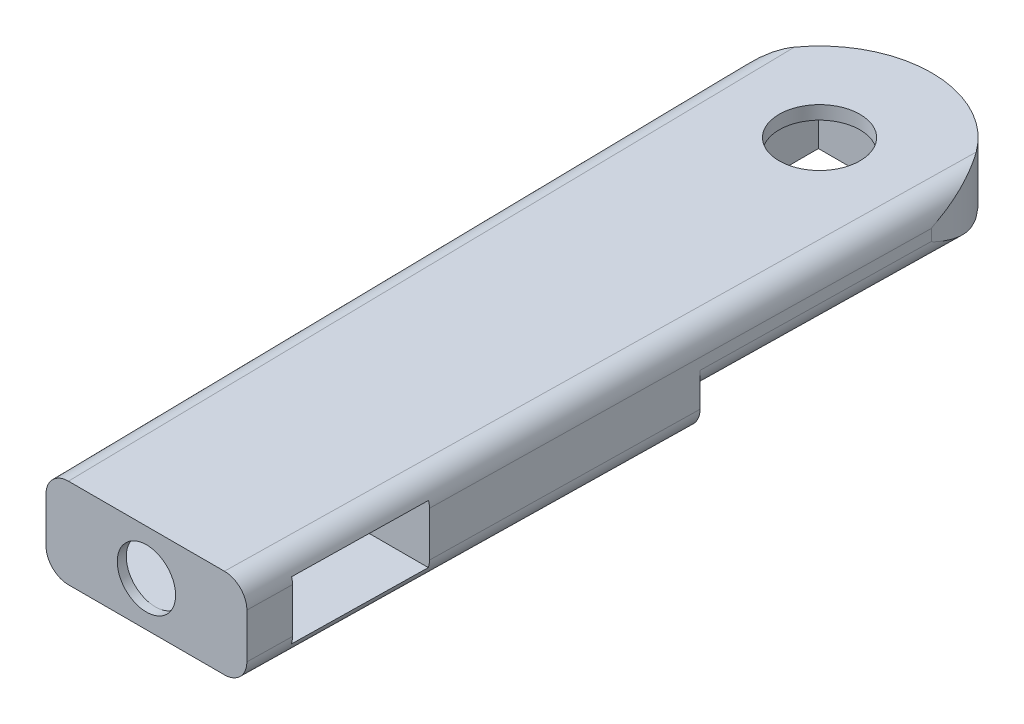
SolidWorks part; units mm, degrees
material "ABS"
ref_plane "Front Plane" through (0, 0, 0) normal (0, 0, 1) x (1, 0, 0)
ref_plane "Top Plane" through (0, 0, 0) normal (0, 1, 0) x (1, 0, 0)
ref_plane "Right Plane" through (0, 0, 0) normal (1, 0, 0) x (0, 0, -1)
sketch "Sketch1" plane through (0, 0, 0) normal (0, 1, 0) x (1, 0, 0)
  line L0 (0, 125.7123) -> (0, -325.7123) construction
  line L1 (-170.4269, -100) -> (232.1141, -100) construction
  line L2 (-25, 0) -> (41.6105, 0) construction
  line L3 (-25, 0) -> (-22.3817, -150)
  line L4 (25, 0) -> (22.3817, -150)
  line L5 (22.3817, -150) -> (-22.3817, -150)
  arc A2 (25, 0) -> (-25, 0) centre (0, 0) ccw
  point P7 (0, -100)
  dimension "D1" = 89
  dimension "D2" = 89
  dimension "D3" = 150
extrude "Boss-Extrude1" add sketch "Sketch1" along normal blind 20
sketch "Sketch7" plane through (0, 0, 0) normal (1, 0, 0) x (0, 0, -1)
  line L0 (-150, 20) -> (-150, 0) construction
  line L1 (-110, 16.4217) -> (-140, 16.4217)
  line L2 (-110, 16.4217) -> (-110, 3.4217)
  line L3 (-110, 3.4217) -> (-140, 3.4217)
  line L4 (-140, 16.4217) -> (-140, 3.4217)
  dimension "D1" = 10
  dimension "D2" = 13
  dimension "D3" = 30
extrude "Cut-Extrude5" cut sketch "Sketch7" against normal through all both and the other way through all
sketch "Sketch8" plane through (0, 0, 140) normal (0, 0, -1) x (-1, 0, 0)
  line L0 (22.5563, 16.4217) -> (22.5563, 3.4217) construction
  line L1 (17.3963, 3.4217) -> (-7.2037, 3.4217)
  line L2 (17.3963, 3.4217) -> (17.3963, 16.4217)
  line L3 (17.3963, 16.4217) -> (-7.2037, 16.4217)
  line L4 (-7.2037, 3.4217) -> (-7.2037, 16.4217)
  line L5 (22.5563, 16.4217) -> (-22.5563, 16.4217) construction
  line L6 (22.5563, 3.4217) -> (-22.5563, 3.4217) construction
  dimension "D1" = 24.6
  dimension "D2" = 5.16
  dimension "D3" = 0
  dimension "D4" = 0
extrude "Cut-Extrude6" cut sketch "Sketch8" against normal blind 8
sketch "Sketch9" plane through (0, 0, 148) normal (0, 0, -1) x (-1, 0, 0)
  line L1 (-22.3817, 20) -> (-22.3817, 0) construction
  line L2 (17.3963, 16.4217) -> (-7.2037, 16.4217) construction
  circle A0 centre (-0.0017, 9.9217) radius 6.5
  dimension "D1" = 13
  dimension "D3" = 6.5
  dimension "D2" = 22.38
extrude "Cut-Extrude7" cut sketch "Sketch9" against normal blind 8
sketch "Sketch10" plane through (0, 0, 0) normal (0, -1, 0) x (1, 0, 0)
  line L1 (10.5, 30.75) -> (-10.5, 30.75)
  line L2 (10.5, 30.75) -> (10.5, -10.25)
  line L3 (10.5, -10.25) -> (-10.5, -10.25)
  line L4 (-10.5, 30.75) -> (-10.5, -10.25)
  arc A0 (-25, 0) -> (25, 0) centre (0, 0) ccw construction
  point P9 (0, -25)
  dimension "D1" = 41
  dimension "D2" = 21
  dimension "D3" = 14.5
  dimension "D4" = 14.75
extrude "Cut-Extrude8" cut sketch "Sketch10" against normal blind 17
sketch "Sketch12" plane through (0, 17, 0) normal (0, -1, 0) x (-1, 0, 0)
  circle A0 centre (0, 0) radius 9
  dimension "D1" = 18
extrude "Cut-Extrude9" cut sketch "Sketch12" against normal blind 12
sketch "Sketch14" plane through (0, 0, 0) normal (0, -1, 0) x (-1, 0, 0)
  line L0 (-10.5, -30.75) -> (10.5, -30.75) construction
  line L1 (10.5, -30.75) -> (10.5, 10.25) construction
  line L2 (-10.5, 10.25) -> (-10.5, -30.75) construction
  line L3 (10.5, 10.25) -> (-10.5, 10.25) construction
  circle A0 centre (-5, -35.45) radius 2
  circle A1 centre (5, -35.45) radius 2
  circle A2 centre (5, 14.95) radius 2
  circle A3 centre (-5, 14.95) radius 2
  dimension "D1" = 4
  dimension "D2" = 4
  dimension "D3" = 4
  dimension "D4" = 4
  dimension "D6" = 4.7
  dimension "D8" = 5.5
  dimension "D9" = 5.5
  dimension "D10" = 5.5
  dimension "D11" = 4.7
  dimension "D12" = 4.7
  dimension "D5" = 4.7
  dimension "D7" = 5.5
extrude "Cut-Extrude11" cut sketch "Sketch14" against normal blind 11.5
sketch "Sketch15" plane through (0, 0, 0) normal (0, -1, 0) x (1, 0, 0)
  line L0 (10.5, 30.75) -> (-10.5, 30.75) construction
  line L1 (37.5576, 50.75) -> (-41.9671, 50.75)
  line L2 (37.5576, 50.75) -> (37.5576, -38.9325)
  line L3 (37.5576, -38.9325) -> (-41.9671, -38.9325)
  line L4 (-41.9671, 50.75) -> (-41.9671, -38.9325)
  dimension "D1" = 20
extrude "Cut-Extrude12" cut sketch "Sketch15" against normal blind 7.5
fillet "Fillet1" radius 5 6 edges at (-23.6909, 20, 75) (-23.2479, 0, 100.375) (-24.5571, 7.5, 25.375) (24.5571, 7.5, 25.375) (23.6909, 20, 75) (23.2479, 0, 100.375)
sketch "Sketch16" plane through (0, 0, 140) normal (0, 0, -1) x (-1, 0, 0)
  circle A0 centre (-8.7017, 9.9217) radius 1
  circle A1 centre (18.8983, 9.9217) radius 1
extrude "Cut-Extrude13" cut sketch "Sketch16" against normal blind 5
